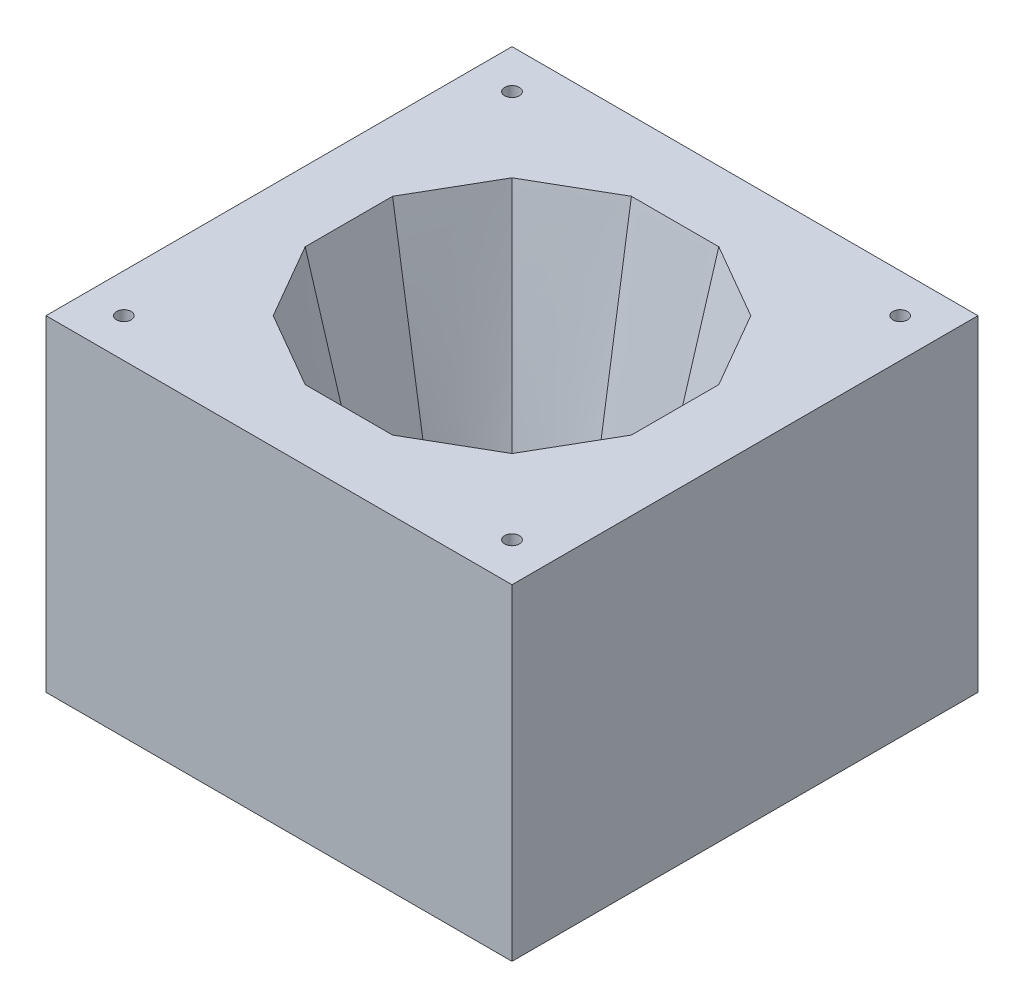
SolidWorks part; units mm, degrees
material "Nylon 101"
ref_plane "Front Plane" through (0, 0, 0) normal (0, 0, 1) x (1, 0, 0)
ref_plane "Top Plane" through (0, 0, 0) normal (0, 1, 0) x (1, 0, 0)
ref_plane "Right Plane" through (0, 0, 0) normal (1, 0, 0) x (0, 0, -1)
sketch "id" plane through (0, 0, 0) normal (0, 1, 0) x (1, 0, 0)
  circle A0 centre (0, 0) radius 25.4
  dimension "D1" = 50.8
ref_plane "Outside face" through (0, 88.9, 0) normal (0, 1, 0) x (1, 0, 0)
sketch "od" plane through (0, 88.9, 0) normal (0, 1, 0) x (1, 0, 0)
  line L1 (44.45, -11.9103) -> (44.45, 11.9103)
  line L2 (44.45, 11.9103) -> (32.5397, 32.5397)
  line L3 (32.5397, 32.5397) -> (11.9103, 44.45)
  line L4 (11.9103, 44.45) -> (-11.9103, 44.45)
  line L5 (-11.9103, 44.45) -> (-32.5397, 32.5397)
  line L6 (-32.5397, 32.5397) -> (-44.45, 11.9103)
  line L7 (-44.45, 11.9103) -> (-44.45, -11.9103)
  line L8 (-44.45, -11.9103) -> (-32.5397, -32.5397)
  line L9 (-32.5397, -32.5397) -> (-11.9103, -44.45)
  line L10 (-11.9103, -44.45) -> (11.9103, -44.45)
  line L11 (11.9103, -44.45) -> (32.5397, -32.5397)
  line L12 (32.5397, -32.5397) -> (44.45, -11.9103)
  circle A0 centre (0, 0) radius 44.45 construction
  dimension "D1" = 88.9
sketch "Sketch3" plane through (0, 88.9, 0) normal (0, 1, 0) x (1, 0, 0)
  line L0 (-48.895, 0) -> (48.895, 0) construction
  line L1 (-63.5, -63.5) -> (63.5, -63.5)
  line L2 (-63.5, -63.5) -> (-63.5, 63.5)
  line L3 (-63.5, 63.5) -> (63.5, 63.5)
  line L4 (63.5, -63.5) -> (63.5, 63.5)
  line L5 (-63.5, -63.5) -> (63.5, 63.5) construction
  line L6 (-63.5, 63.5) -> (63.5, -63.5) construction
  line L7 (0, -48.895) -> (0, 48.895) construction
  circle A0 centre (-52.8934, 52.8934) radius 2
  circle A1 centre (-52.8934, -52.8934) radius 2
  circle A2 centre (52.8934, -52.8934) radius 2
  circle A3 centre (52.8934, 52.8934) radius 2
  point P0 (0, 0)
  point P6 (-53.0546, 53.0546)
  dimension "D2" = 4
  dimension "D1" = 127
  dimension "D3" = 15
extrude "Boss-Extrude1" add sketch "Sketch3" against normal up to surface (88.9 mm away) contours L1 L4 L3 L2 A1 A0 A2 A3 | A1 | A2 | A3 | A0 region at (0, 88.9, 0) region at (-52.8934, 88.9, -52.8934) region at (-52.8934, 88.9, 52.8934) region at (52.8934, 88.9, 52.8934) region at (52.8934, 88.9, -52.8934) up to plane "Top Plane"
extrude "Cut-Extrude1" cut sketch "Sketch3<3>" against normal blind 30 contours A1 | A2 | A3 | A0 region at (-52.8934, 88.9, -52.8934) region at (-52.8934, 88.9, 52.8934) region at (52.8934, 88.9, 52.8934) region at (52.8934, 88.9, -52.8934)
sketch "Sketch3<3>" plane through (0, 88.9, 0) normal (0, 1, 0) x (1, 0, 0) same geometry as "Sketch3"
loft "Cut-Loft1" cut profiles "od", "id" connector at (-32.5397, 88.9, 32.5397) connector at (-6.8408, 0, 24.4615)
equation "\"id\"= 2in"
equation "\"od\"= 4in"
equation "\"h\"= 3.5in"
equation "\"D1@id\" = \"id\""
equation "\"D1@od\" = \"h\""
